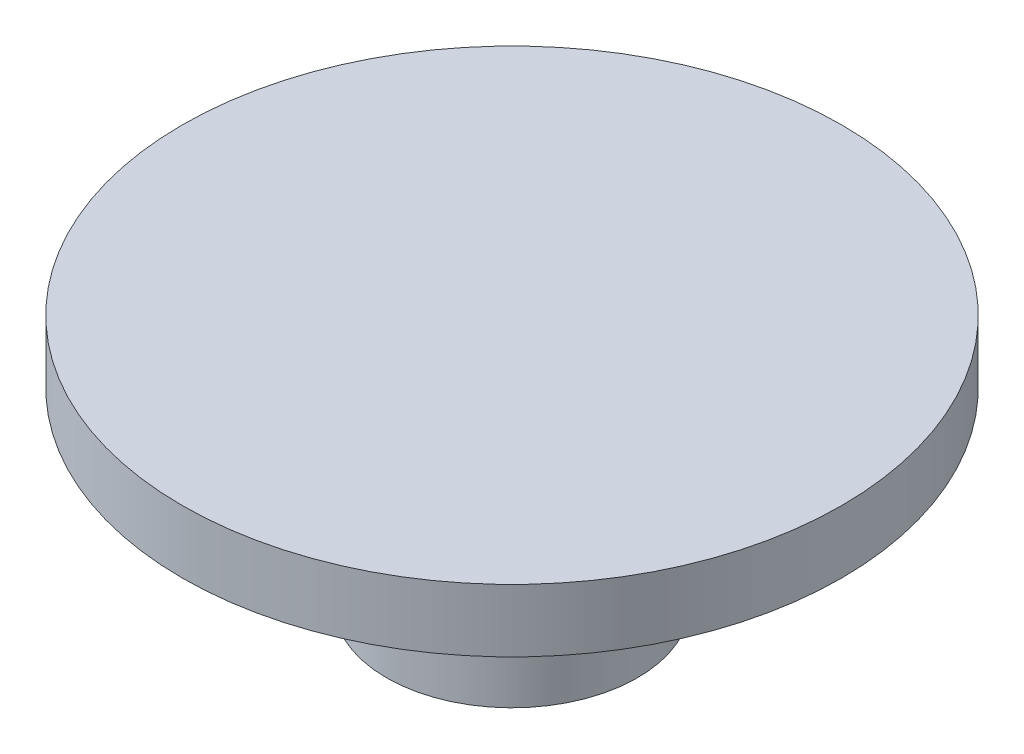
SolidWorks part; units mm, degrees
material "Polyetheretherketone (PEEK)"
ref_plane "Front Plane" through (0, 0, 0) normal (0, 0, 1) x (1, 0, 0)
ref_plane "Top Plane" through (0, 0, 0) normal (0, 1, 0) x (1, 0, 0)
ref_plane "Right Plane" through (0, 0, 0) normal (1, 0, 0) x (0, 0, -1)
sketch "Sketch1" plane through (0, 0, 0) normal (0, 1, 0) x (1, 0, 0)
  circle A0 centre (0, 0) radius 4
  dimension "D1" = 8
extrude "Boss-Extrude1" add sketch "Sketch1" along normal blind 6
sketch "Sketch2" plane through (0, 6, 0) normal (0, 1, 0) x (1, 0, 0)
  circle A0 centre (0, 0) radius 10.5
  dimension "D1" = 21
extrude "Boss-Extrude2" add sketch "Sketch2" along normal blind 2
ref_axis "Axis1" through (0, 6, 0) along (0, -1, 0)
